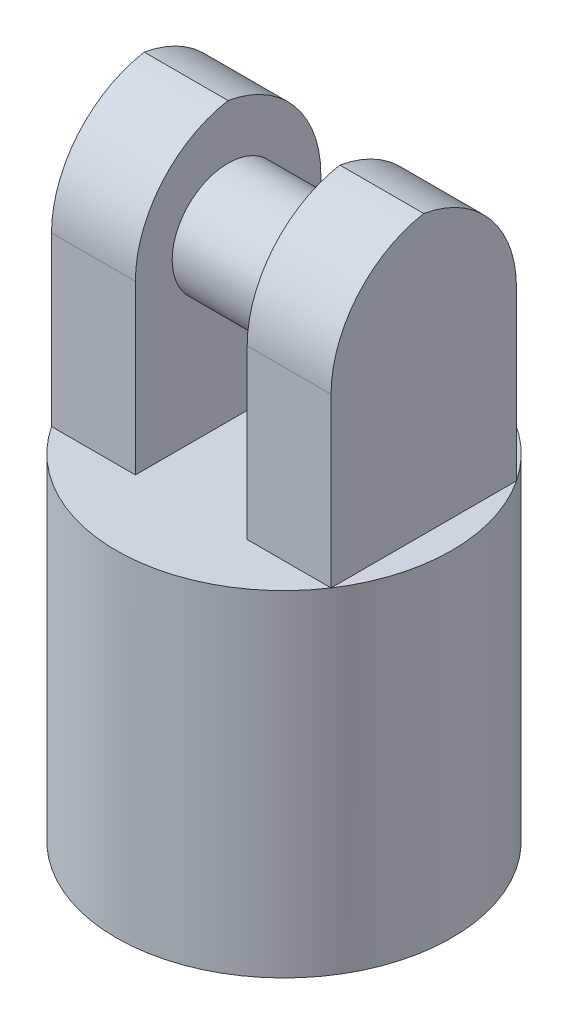
SolidWorks part; units mm, degrees
ref_plane "Front Plane" through (0, 0, 0) normal (0, 0, 1) x (1, 0, 0)
ref_plane "Top Plane" through (0, 0, 0) normal (0, 1, 0) x (1, 0, 0)
ref_plane "Right Plane" through (0, 0, 0) normal (1, 0, 0) x (0, 0, -1)
sketch "Sketch1" plane through (0, 0, 0) normal (0, 1, 0) x (1, 0, 0)
  circle A0 centre (0, 0) radius 38.1
  dimension "D1" = 76.2
extrude "Boss-Extrude1" add sketch "Sketch1" along normal blind 76.2
sketch "Sketch2" plane through (0, 76.2, 0) normal (0, 1, 0) x (1, 0, 0)
  line L1 (-31.75, -21.0606) -> (31.75, -21.0606)
  line L2 (-31.75, -21.0606) -> (-31.75, 21.0606)
  line L3 (-31.75, 21.0606) -> (31.75, 21.0606)
  line L4 (31.75, -21.0606) -> (31.75, 21.0606)
  line L5 (-31.75, -21.0606) -> (31.75, 21.0606) construction
  line L6 (-31.75, 21.0606) -> (31.75, -21.0606) construction
  circle A0 centre (0, 0) radius 38.1 construction
  point P0 (0, 0)
  dimension "D1" = 63.5
extrude "Boss-Extrude2" add sketch "Sketch2" along normal blind 63.5
sketch "Sketch3" plane through (0, 139.7, 0) normal (0, 1, 0) x (1, 0, 0)
  line L0 (31.75, 21.0606) -> (-31.75, 21.0606) construction
  line L1 (-12.7, -21.0606) -> (12.7, -21.0606)
  line L2 (-12.7, -21.0606) -> (-12.7, 21.0606)
  line L3 (-12.7, 21.0606) -> (12.7, 21.0606)
  line L4 (12.7, -21.0606) -> (12.7, 21.0606)
  line L5 (-12.7, -21.0606) -> (12.7, 21.0606) construction
  line L6 (-12.7, 21.0606) -> (12.7, -21.0606) construction
  point P0 (0, 0)
  dimension "D1" = 25.4
extrude "Cut-Extrude1" cut sketch "Sketch3" against normal blind 63.5
fillet "Fillet1" radius 25.4 4 edges at (-22.225, 139.7, -21.0606) (-22.225, 139.7, 21.0606) (22.225, 139.7, -21.0606) (22.225, 139.7, 21.0606)
sketch "Sketch5" plane through (0, 0, 0) normal (0, -1, 0) x (1, 0, 0)
  circle A0 centre (0, 0) radius 25.4
extrude "Cut-Extrude3" cut sketch "Sketch5" against normal blind 50.8
sketch "Sketch6" plane through (31.75, 0, 0) normal (1, 0, 0) x (0, 0, -1)
  circle A0 centre (0, 114.3) radius 12.7
extrude "Boss-Extrude3" add sketch "Sketch6" against normal blind 53.34
